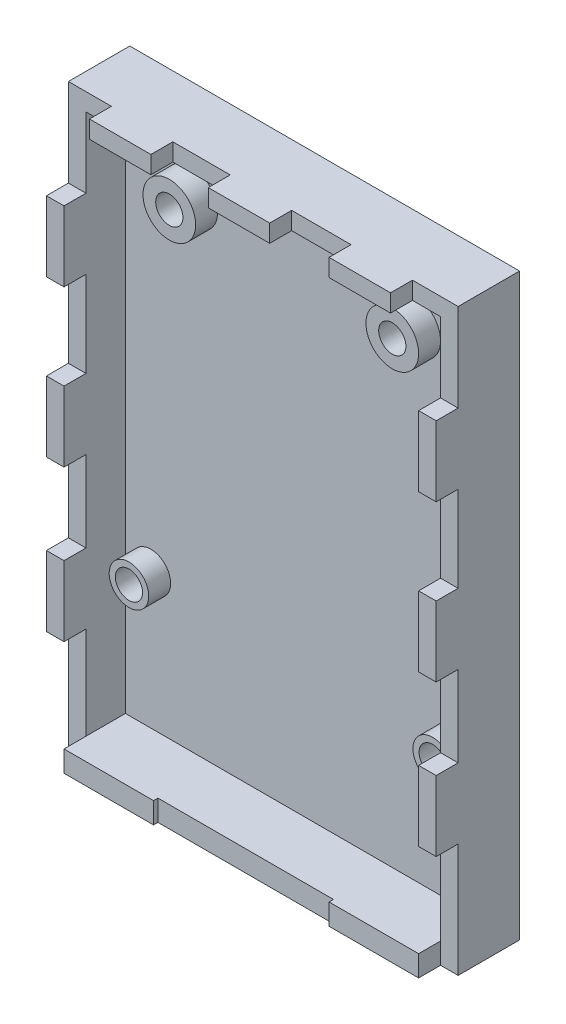
SolidWorks part; units mm, degrees
note: The reader was unsure of these and kept them because the rebuilt part matched: shared geometry of "Esboço1<3>", "Esboço1<4>", "Esboço1<5>", "Esboço1<6>".
ref_plane "Plano frontal" through (0, 0, 0) normal (0, 0, 1) x (1, 0, 0)
ref_plane "Plano superior" through (0, 0, 0) normal (0, 1, 0) x (1, 0, 0)
ref_plane "Plano direito" through (0, 0, 0) normal (1, 0, 0) x (0, 0, -1)
sketch "Esboço1" plane through (0, 0, 0) normal (0, 0, 1) x (1, 0, 0)
  line L0 (-22.694, -49.6652) -> (-24.694, -49.6652)
  line L1 (-22.694, 14.3348) -> (17.706, 14.3348)
  line L2 (-22.694, 14.3348) -> (-22.694, -49.6652)
  line L3 (-22.694, -49.6652) -> (17.706, -49.6652)
  line L4 (17.706, 14.3348) -> (17.706, -49.6652)
  line L5 (-22.694, -49.6652) -> (17.706, -49.6652)
  line L6 (-22.694, -49.6652) -> (-22.694, -47.2652)
  line L7 (-22.694, -47.2652) -> (17.706, -47.2652)
  line L8 (17.706, -49.6652) -> (17.706, -47.2652)
  line L9 (-24.694, 16.3348) -> (19.706, 16.3348)
  line L10 (-24.694, 16.3348) -> (-24.694, -49.6652)
  line L11 (17.706, -49.6652) -> (19.706, -49.6652)
  line L12 (19.706, 16.3348) -> (19.706, -49.6652)
  line L13 (-12.494, -47.2652) -> (7.506, -47.2652)
  line L14 (-12.494, -47.2652) -> (-12.494, -49.6652)
  line L15 (-12.494, -49.6652) -> (7.506, -49.6652)
  line L16 (7.506, -47.2652) -> (7.506, -49.6652)
  line L18 (-24.694, 6.3115) -> (-22.694, 6.3115)
  line L19 (-24.694, 6.3115) -> (-24.694, -1.6885)
  line L20 (-24.694, -1.6885) -> (-22.694, -1.6885)
  line L21 (-22.694, 6.3115) -> (-22.694, -1.6885)
  line L22 (-24.694, -11.4682) -> (-22.694, -11.4682)
  line L23 (-24.694, -11.4682) -> (-24.694, -19.4682)
  line L24 (-24.694, -19.4682) -> (-22.694, -19.4682)
  line L25 (-22.694, -11.4682) -> (-22.694, -19.4682)
  line L26 (17.706, 6.3115) -> (19.706, 6.3115)
  line L27 (17.706, 6.3115) -> (17.706, -1.6885)
  line L28 (17.706, -1.6885) -> (19.706, -1.6885)
  line L29 (19.706, 6.3115) -> (19.706, -1.6885)
  line L30 (17.706, -11.4682) -> (19.706, -11.4682)
  line L31 (17.706, -11.4682) -> (17.706, -19.4682)
  line L32 (17.706, -19.4682) -> (19.706, -19.4682)
  line L33 (19.706, -11.4682) -> (19.706, -19.4682)
  line L34 (-24.694, -28.6888) -> (-22.694, -28.6888)
  line L35 (-24.694, -28.6888) -> (-24.694, -36.6888)
  line L36 (-24.694, -36.6888) -> (-22.694, -36.6888)
  line L37 (-22.694, -28.6888) -> (-22.694, -36.6888)
  line L38 (17.706, -28.6888) -> (19.706, -28.6888)
  line L39 (17.706, -28.6888) -> (17.706, -36.6888)
  line L40 (17.706, -36.6888) -> (19.706, -36.6888)
  line L41 (19.706, -28.6888) -> (19.706, -36.6888)
  line L42 (-19.794, 16.3348) -> (-12.794, 16.3348)
  line L43 (-19.794, 16.3348) -> (-19.794, 14.3348)
  line L44 (-19.794, 14.3348) -> (-12.794, 14.3348)
  line L45 (-12.794, 16.3348) -> (-12.794, 14.3348)
  line L46 (14.506, 14.3348) -> (7.506, 14.3348)
  line L47 (14.506, 14.3348) -> (14.506, 16.3348)
  line L48 (14.506, 16.3348) -> (7.506, 16.3348)
  line L49 (7.506, 14.3348) -> (7.506, 16.3348)
  line L50 (-6.2581, 16.3348) -> (0.7419, 16.3348)
  line L51 (-6.2581, 16.3348) -> (-6.2581, 14.3348)
  line L52 (-6.2581, 14.3348) -> (0.7419, 14.3348)
  line L53 (0.7419, 16.3348) -> (0.7419, 14.3348)
  circle A0 centre (-15.194, 7.4348) radius 1.55
  circle A1 centre (10.206, 7.4348) radius 1.55
  circle A2 centre (-19.794, -31.8652) radius 1.55
  circle A3 centre (14.806, -31.8652) radius 1.55
  circle A4 centre (-15.194, 7.4348) radius 3
  circle A5 centre (10.206, 7.4348) radius 3
  circle A6 centre (-19.794, -31.8652) radius 2.25
  circle A7 centre (14.806, -31.8652) radius 2.25
  point P63 (0, 0)
  dimension "D5" = 3.1
  dimension "D6" = 3.1
  dimension "D7" = 3.1
  dimension "D8" = 3.1
  dimension "D20" = 6
  dimension "D21" = 6
  dimension "D22" = 4.5
  dimension "D23" = 4.5
  dimension "D1" = 40.4
  dimension "D2" = 64
  dimension "D3" = 6.9
  dimension "D4" = 6.9
  dimension "D9" = 7.5
  dimension "D10" = 7.5
  dimension "D11" = 2.9
  dimension "D12" = 2.9
  dimension "D13" = 17.8
  dimension "D14" = 17.8
  dimension "D15" = 2.4
  dimension "D16" = 2
  dimension "D17" = 2
  dimension "D18" = 2
  dimension "D19" = 8
  dimension "D24" = 20
  dimension "D25" = 8
  dimension "D26" = 8
  dimension "D27" = 8
  dimension "D28" = 8
  dimension "D29" = 8
  dimension "D30" = 7
  dimension "D31" = 7
  dimension "D32" = 7
extrude "Ressalto-extrusão1" add sketch "Esboço1" along normal blind 2.5
extrude "Ressalto-extrusão2" add sketch "Esboço1<3>" along normal blind 5 contours A4 A0 | A5 A1 | A6 A2 | A7 A3
sketch "Esboço1<3>" plane through (0, 0, 0) normal (0, 0, 1) x (1, 0, 0) same geometry as "Esboço1"
extrude "Ressalto-extrusão3" add sketch "Esboço1<4>" along normal blind 9 contours L7 L2 L3 L4
sketch "Esboço1<4>" plane through (0, 0, 0) normal (0, 0, 1) x (1, 0, 0) same geometry as "Esboço1"
extrude "Ressalto-extrusão4" add sketch "Esboço1<5>" along normal blind 7 contours L43 L9 L10 L18 L2 L1 | L10 L20 L2 L18 | L10 L22 L2 L20 | L10 L24 L2 L22 | L10 L34 L2 L24 | L10 L36 L2 L34 | L36 L10 L0 L2 | L14 L7 L2 L3 | L7 L16 L3 L4 | L40 L4 L11 L12 | L4 L40 L12 L38 | L4 L38 L12 L32 | L4 L32 L12 L30 | L4 L30 L12 L28 | L4 L28 L12 L26 | L47 L1 L4 L26 L12 L9 | L49 L1 L47 L9 | L9 L53 L1 L49 | L53 L9 L51 L1 | L51 L9 L45 L1 | L45 L9 L43 L1
sketch "Esboço1<5>" plane through (0, 0, 0) normal (0, 0, 1) x (1, 0, 0) same geometry as "Esboço1"
extrude "Ressalto-extrusão5" add sketch "Esboço1<6>" along normal blind 9.5 contours L10 L20 L2 L18 | L10 L24 L2 L22 | L10 L36 L2 L34 | L14 L7 L2 L3 | L7 L16 L3 L4 | L4 L40 L12 L38 | L4 L32 L12 L30 | L4 L28 L12 L26 | L49 L1 L47 L9 | L53 L9 L51 L1 | L45 L9 L43 L1
sketch "Esboço1<6>" plane through (0, 0, 0) normal (0, 0, 1) x (1, 0, 0) same geometry as "Esboço1"
